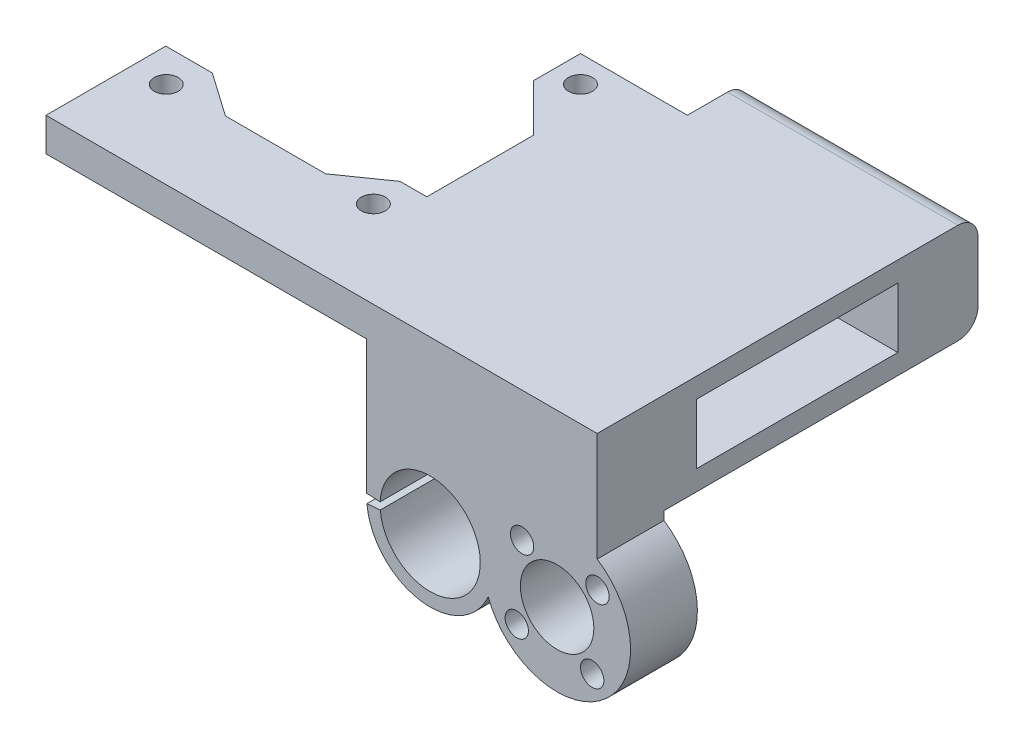
SolidWorks part; units mm, degrees
ref_plane "Front Plane" through (0, 0, 0) normal (0, 0, 1) x (1, 0, 0)
ref_plane "Top Plane" through (0, 0, 0) normal (0, 1, 0) x (1, 0, 0)
ref_plane "Right Plane" through (0, 0, 0) normal (1, 0, 0) x (0, 0, -1)
sketch "Sketch1" plane through (0, 0, 0) normal (0, 1, 0) x (1, 0, 0)
  line L0 (0, 0) -> (82.5, 0)
  line L1 (82.5, 0) -> (82.5, 57)
  line L2 (82.5, 57) -> (48, 57)
  line L3 (48, 57) -> (48, 48)
  line L4 (48, 48) -> (32, 48)
  line L5 (32, 48) -> (32, 41)
  line L6 (32, 41) -> (39.0711, 33.9289)
  line L7 (39.0711, 33.9289) -> (39.0711, 17.9289)
  line L8 (39.0711, 17.9289) -> (35.0711, 17.9289)
  line L9 (35.0711, 17.9289) -> (28.5179, 13.3403)
  line L10 (28.5179, 13.3403) -> (13.5179, 13.3403)
  line L11 (13.5179, 13.3403) -> (6.9646, 17.9289)
  line L12 (6.9646, 17.9289) -> (0, 17.9289)
  line L13 (0, 17.9289) -> (0, 0)
  line L14 (36, 44) -> (36, 13) construction
  line L15 (36, 13) -> (5, 13) construction
  circle A0 centre (5, 13) radius 1.8
  circle A1 centre (36, 13) radius 1.8
  circle A2 centre (36, 44) radius 1.8
  dimension "D16" = 3.6
  dimension "D18" = 13
  dimension "D19" = 5
  dimension "D1" = 82.5
  dimension "D2" = 57
  dimension "D3" = 34.5
  dimension "D4" = 9
  dimension "D5" = 16
  dimension "D6" = 7
  dimension "D7" = 10
  dimension "D8" = 135
  dimension "D9" = 16
  dimension "D10" = 4
  dimension "D11" = 8
  dimension "D12" = 145
  dimension "D13" = 15
  dimension "D14" = 8
  dimension "D15" = 145
  dimension "D17" = 31
extrude "Boss-Extrude1" add sketch "Sketch1" along normal blind 35 contours L12 L13 L0 L1 L2 L3 L4 L5 L6 L7 L8 L9 L10 L11 A2 A1 A0 region at (52.7755, 0, -24.1718)
sketch "Sketch2" plane through (0, 0, 0) normal (0, -1, 0) x (1, 0, 0)
  line L0 (82.5, -57) -> (82.5, 0)
  line L1 (82.5, 0) -> (67, 0)
  line L2 (0, 0) -> (82.5, 0) construction
  line L3 (67, 0) -> (67, -48)
  line L4 (67, -48) -> (48, -48)
  line L5 (48, -48) -> (48, -57)
  line L6 (82.5, -57) -> (48, -57) construction
  line L7 (48, -57) -> (82.5, -57)
  dimension "D1" = 15.5
extrude "Cut-Extrude1" cut sketch "Sketch2" against normal blind 20
fillet "Fillet1" radius 3 2 edges at (65.25, 35, -57) (65.25, 20, -57)
sketch "Sketch3" plane through (0, 0, -48) normal (0, 0, -1) x (-1, 0, 0)
  line L0 (-67, 0) -> (-32, 0) construction
  line L1 (-67, 20) -> (-67, 0) construction
  line L2 (-50.0285, 8.8463) -> (-48.0362, 8.672)
  line L3 (-67, 0) -> (-48, 0)
  line L4 (-67, 0) -> (-67, 20)
  line L5 (-67, 20) -> (-48, 20)
  line L6 (-48, 0) -> (-48, 20)
  line L7 (-48.013, 9.9972) -> (-50.0103, 9.8925)
  line L8 (-50.0285, 8.8463) -> (-57.5, 9.5) construction
  line L9 (-57.5, 9.5) -> (-57.5, 0) construction
  line L10 (-48.013, 9.9972) -> (-48, 9.9979)
  circle A0 centre (-57.5, 9.5) radius 9.5
  circle A1 centre (-57.5, 9.5) radius 7.5
  line M1 (-67, 0) -> (-32, 0)
  line M5 (-48, 20) -> (-67, 20)
  dimension "D1" = 19
  dimension "D2" = 15
  dimension "D3" = 8
  dimension "D4" = 85
extrude "Cut-Extrude2" cut sketch "Sketch3" against normal through all both and the other way through all contours A1 M5 | A1 M5 | A0 L4 M1 | A1 L2 A0 L7 | A0 L3 L6 | A0 L6 L10 region at (48.969, 9.3511, -48) region at (57.5, 9.5, -48) region at (50.122, 2.122, -48) region at (48.0039, 9.8732, -48) region at (64.878, 2.122, -48)
sketch "Sketch5" plane through (0, 0, 0) normal (0, -1, 0) x (1, 0, 0)
  line L1 (48, -48) -> (0, -48)
  line L2 (48, -48) -> (48, 0)
  line L3 (48, 0) -> (0, 0)
  line L4 (0, -48) -> (0, 0)
extrude "Cut-Extrude3" cut sketch "Sketch5" against normal blind 30
sketch "Sketch6" plane through (82.5, 0, 0) normal (1, 0, 0) x (0, 0, -1)
  line L0 (45, 27.5) -> (57, 27.5) construction
  line L1 (14.858, 32) -> (45, 32)
  line L2 (14.858, 32) -> (14.858, 23)
  line L3 (14.858, 23) -> (45, 23)
  line L4 (45, 32) -> (45, 23)
  line L6 (57, 32) -> (57, 23) construction
  dimension "D1" = 9
  dimension "D2" = 30.142
  dimension "D3" = 12
extrude "Cut-Extrude4" cut sketch "Sketch6" against normal blind 31.4
sketch "Sketch7" plane through (51.1, 0, 0) normal (1, 0, 0) x (0, 0, -1)
  line L0 (14.858, 23) -> (45, 23) construction
  line L3 (17.9289, 23) -> (38.9289, 23)
  line L4 (17.9289, 23) -> (17.9289, 32)
  line L7 (17.9289, 32) -> (38.9289, 32)
  line L8 (38.9289, 23) -> (38.9289, 32)
  line L9 (45, 32) -> (14.858, 32) construction
  dimension "D1" = 21
extrude "Cut-Extrude5" cut sketch "Sketch7" against normal through all
sketch "Sketch8" plane through (0, 30, 0) normal (0, -1, 0) x (1, 0, 0)
  circle A0 centre (5, -13) radius 3.5
  circle A1 centre (36, -13) radius 3.5
  circle A2 centre (36, -44) radius 3.5
  dimension "D1" = 7
extrude "Cut-Extrude6" cut sketch "Sketch8" against normal blind 1.5
sketch "Sketch11" plane through (0, 0, 0) normal (0, 0, 1) x (1, 0, 0)
  line L0 (76.5, 9.5) -> (57.5, 9.5) construction
  line L1 (65.5, 9.5) -> (65.5, 20.5)
  line L2 (65.5, 20.5) -> (76.5, 20.5)
  line L3 (76.5, 9.5) -> (76.5, 17.5) construction
  line L4 (82.5377, 14.7485) -> (70.4623, 4.2515) construction
  line L5 (71.2515, 15.5377) -> (81.7485, 3.4623) construction
  line L6 (82.5, 20) -> (82.5, 18.7195)
  circle A0 centre (76.5, 9.5) radius 11
  circle A1 centre (76.5, 9.5) radius 5.5
  circle A2 centre (76.5, 9.5) radius 8 construction
  circle A3 centre (82.5377, 14.7485) radius 1.75
  circle A4 centre (81.7485, 3.4623) radius 1.75
  circle A5 centre (70.4623, 4.2515) radius 1.75
  circle A6 centre (71.2515, 15.5377) radius 1.75
  arc M10 (48.0362, 8.672) -> (67, 9.5) centre (57.5, 9.5) ccw
  line M11 (67, 9.5) -> (67, 20)
  line M12 (67, 20) -> (82.5, 20)
  dimension "D1" = 22
  dimension "D3" = 11
  dimension "D4" = 16
  dimension "D6" = 3.5
  dimension "D2" = 19
  dimension "D5" = 41
extrude "Boss-Extrude3" add sketch "Sketch11" against normal blind 10 contours A6 A0 M12 M11 | A6 A0 A5 A4 A3 A1 M11 M10 M12 | A0 L6 M12 region at (68.7783, 18.5541, 0) region at (69.8358, 17.8678, 0) region at (81.6518, 19.5969, 0)
